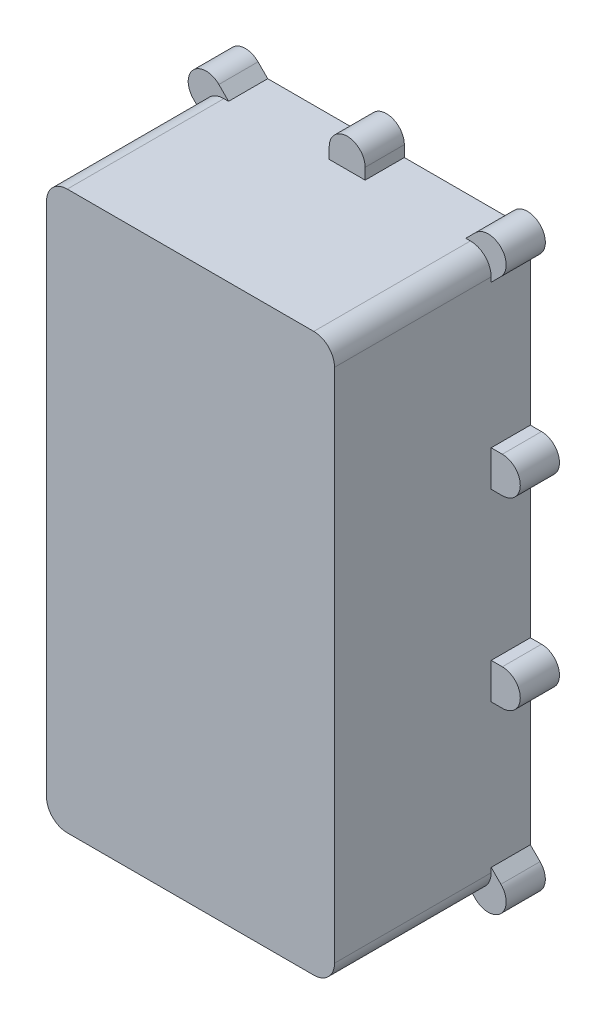
SolidWorks part; units mm, degrees
material "ABS"
ref_plane "X-Y Datum" through (0, 0, 0) normal (0, 0, 1) x (1, 0, 0)
ref_plane "X-Z Datum" through (0, 0, 0) normal (0, 1, 0) x (1, 0, 0)
ref_plane "Y-Z Datum" through (0, 0, 0) normal (1, 0, 0) x (0, 0, -1)
sketch "Sketch1" plane through (0, 0, 0) normal (0, 0, 1) x (1, 0, 0)
  line L0 (1.8162, 48.1563) -> (125.4513, 48.1563) construction
  line L1 (24.3593, 48.1563) -> (24.3593, 120.2923) construction
  line L3 (24.3593, 120.2923) -> (125.4513, 120.2923) construction
  line L8 (125.4513, 48.1563) -> (125.4513, 120.2923) construction
  line L33 (24.3593, 120.2923) -> (1.8162, 120.2923) construction
  line L34 (24.3593, 120.2923) -> (24.3593, 48.1563) construction
  line L35 (63.6337, 48.1563) -> (63.6337, 43.0763) construction
  line L36 (1.8162, 120.2923) -> (1.8162, 48.1563) construction
  line L41 (24.3593, 120.2923) -> (23.7243, 120.2923) construction
  line L42 (24.3593, 120.2923) -> (24.3593, 122.8323) construction
  line L44 (27.5343, 14.7553) -> (27.5343, 43.0763) construction
  line L45 (125.4513, 120.2923) -> (127.9913, 120.2923) construction
  line L46 (27.5343, 14.7553) -> (125.4513, 14.7553) construction
  line L47 (23.7243, 122.8323) -> (127.9913, 122.8323)
  line L48 (23.7243, 122.8323) -> (23.7243, -21.9477)
  line L49 (23.7243, -21.9477) -> (127.9913, -21.9477)
  line L50 (127.9913, 122.8323) -> (127.9913, -21.9477)
  line L51 (125.4513, 14.7553) -> (125.4513, 43.0763) construction
  line L52 (27.5343, 43.0763) -> (125.4513, 43.0763) construction
  line L53 (23.7243, 120.2923) -> (23.7243, 48.1563) construction
  circle A17 centre (30.4553, 114.1963) radius 2.1 construction
  circle A18 centre (119.8633, 115.2123) radius 2.1 construction
  circle A19 centre (119.6813, 54.2533) radius 2.1 construction
  circle A20 centre (29.4393, 53.2363) radius 2.1 construction
  circle A26 centre (31.9793, 18.4383) radius 2.1 construction
  circle A27 centre (31.9793, 39.3933) radius 2.1 construction
  circle A28 centre (120.6193, 28.8183) radius 2.1 construction
sketch "Sketch2" plane through (0, 0, 0) normal (0, 0, 1) x (1, 0, 0)
  line L4 (55.176, 122.8323) -> (127.9913, 122.8323)
  line L6 (55.176, 48.5244) -> (55.176, 50.9244) construction
  line L7 (55.176, -21.05) -> (127.9913, -21.05)
  line L8 (127.9913, 122.8323) -> (127.9913, -21.05)
  line L9 (55.176, 110.2103) -> (127.9913, -21.05) construction
  line L10 (55.176, -8.428) -> (127.9913, 122.8323) construction
  line L11 (55.176, 50.9244) -> (55.176, -21.05)
  line L12 (55.176, 50.9244) -> (55.176, 122.8323)
  circle A7 centre (88.0827, 6.45) radius 27.5
  circle A8 centre (88.0294, 95.3501) radius 27.5
  circle A9 centre (98.216, 50.8911) radius 6.477
  circle A10 centre (77.896, 50.9089) radius 6.477
  circle A11 centre (121.5143, 31.8208) radius 6.477
  circle A12 centre (115.996, 50.8756) radius 2.4
  circle A13 centre (55.176, 50.9244) radius 2.4
  point P14 (88.0827, 50.8911)
sketch "Sketch3" plane through (0, 0, 0) normal (0, 0, 1) x (1, 0, 0)
  line L7 (0, 0) -> (76.2, 0)
  line L10 (0, 0) -> (0, 158.75)
  line L11 (0, 158.75) -> (76.2, 158.75)
  line L12 (76.2, 0) -> (76.2, 158.75)
  dimension "D1" = 158.75
  dimension "D2" = 76.2
extrude "Boss-Extrude1" add sketch "Sketch3" along normal blind 53.975
shell "Shell1" thickness 6 removed face at (38.1, 79.375, 0) outward yes
fillet "Fillet1" radius 5.334 4 edges at (76.2, 158.75, 26.9875) (76.2, 0, 26.9875) (0, 0, 26.9875) (0, 158.75, 26.9875)
fillet "Fillet2" radius 6.35 4 edges at (-6, -6, 29.9875) (-6, 164.75, 29.9875) (82.2, 164.75, 29.9875) (82.2, -6, 29.9875)
sketch "Sketch6" plane through (0, 0, 0) normal (0, 0, -1) x (-1, 0, 0)
  line L8 (-5.334, 163.0327) -> (-70.866, 163.0327)
  line L9 (-80.4827, 153.416) -> (-80.4827, 5.334)
  line L10 (-70.866, -4.2827) -> (-5.334, -4.2827)
  line L11 (4.2827, 5.334) -> (4.2827, 153.416)
  line L12 (-79.2, 153.416) -> (-79.2, 5.334)
  line L13 (-70.866, -3) -> (-5.334, -3)
  line L14 (3, 5.334) -> (3, 153.416)
  line L15 (-5.334, 161.75) -> (-70.866, 161.75)
  line L16 (-79.2, 153.416) -> (-79.2, 5.334) construction
  line L17 (-70.866, -3) -> (-5.334, -3) construction
  line L18 (3, 5.334) -> (3, 153.416) construction
  line L19 (-5.334, 161.75) -> (-70.866, 161.75) construction
  line L20 (-77.9173, 153.416) -> (-77.9173, 5.334)
  line L21 (-70.866, -1.7173) -> (-5.334, -1.7173)
  line L22 (1.7173, 5.334) -> (1.7173, 153.416)
  line L23 (-5.334, 160.4673) -> (-70.866, 160.4673)
  arc A8 (-70.866, 163.0327) -> (-80.4827, 153.416) centre (-70.866, 153.416) ccw
  arc A9 (-80.4827, 5.334) -> (-70.866, -4.2827) centre (-70.866, 5.334) ccw
  arc A10 (-5.334, -4.2827) -> (4.2827, 5.334) centre (-5.334, 5.334) ccw
  arc A11 (4.2827, 153.416) -> (-5.334, 163.0327) centre (-5.334, 153.416) ccw
  arc A12 (-70.866, 161.75) -> (-79.2, 153.416) centre (-70.866, 153.416) ccw
  arc A13 (-79.2, 5.334) -> (-70.866, -3) centre (-70.866, 5.334) ccw
  arc A14 (-5.334, -3) -> (3, 5.334) centre (-5.334, 5.334) ccw
  arc A15 (3, 153.416) -> (-5.334, 161.75) centre (-5.334, 153.416) ccw
  arc A16 (-70.866, 161.75) -> (-79.2, 153.416) centre (-70.866, 153.416) ccw construction
  arc A17 (-79.2, 5.334) -> (-70.866, -3) centre (-70.866, 5.334) ccw construction
  arc A18 (-5.334, -3) -> (3, 5.334) centre (-5.334, 5.334) ccw construction
  arc A19 (3, 153.416) -> (-5.334, 161.75) centre (-5.334, 153.416) ccw construction
  arc A20 (-77.9173, 5.334) -> (-70.866, -1.7173) centre (-70.866, 5.334) ccw
  arc A21 (-5.334, -1.7173) -> (1.7173, 5.334) centre (-5.334, 5.334) ccw
  arc A22 (1.7173, 153.416) -> (-5.334, 160.4673) centre (-5.334, 153.416) ccw
  arc A23 (-70.866, 160.4673) -> (-77.9173, 153.416) centre (-70.866, 153.416) ccw
  dimension "D4" = 7.0513
  dimension "D5" = 2.5654
  dimension "D1" = 3
  dimension "D2" = 1.2827
  dimension "D3" = 1.2827
extrude "Cut-Extrude1" cut sketch "Sketch6" against normal blind 1.2446
fillet "Fillet3" radius 0.254 16 edges at (-4.2827, 79.375, 1.2446) (-1.466, -1.466, 1.2446) (38.1, -4.2827, 1.2446) (77.666, -1.466, 1.2446) (80.4827, 79.375, 1.2446) (77.666, 160.216, 1.2446) (38.1, 163.0327, 1.2446) (-1.466, 160.216, 1.2446) (75.852, 158.402, 1.2446) (77.9173, 79.375, 1.2446) (75.852, 0.348, 1.2446) (38.1, -1.7173, 1.2446) (0.348, 0.348, 1.2446) (-1.7173, 79.375, 1.2446) (0.348, 158.402, 1.2446) (38.1, 160.4673, 1.2446)
fillet "Fillet4" radius 0.127 16 edges at (75.852, 158.402, 0) (38.1, 160.4673, 0) (0.348, 158.402, 0) (-1.7173, 79.375, 0) (0.348, 0.348, 0) (38.1, -1.7173, 0) (75.852, 0.348, 0) (77.666, 160.216, 0) (38.1, 163.0327, 0) (-1.466, 160.216, 0) (-4.2827, 79.375, 0) (-1.466, -1.466, 0) (38.1, -4.2827, 0) (77.666, -1.466, 0) (77.9173, 79.375, 0) (80.4827, 79.375, 0)
sketch "Sketch7" plane through (0, 0, 53.975) normal (0, 0, -1) x (-1, 0, 0)
  line L0 (-76.2, 34.925) -> (0, 34.925)
  line L1 (-76.2, 5.334) -> (-76.2, 153.416) construction
  line L2 (0, 153.416) -> (0, 5.334) construction
  line L3 (-76.2, 37.425) -> (0, 37.425)
  line L4 (-5.334, 0) -> (-70.866, 0) construction
  line L5 (-76.2, 34.925) -> (-76.2, 37.425)
  line L6 (0, 34.925) -> (0, 37.425)
  dimension "D2" = 34.925
  dimension "D1" = 2.5
extrude "Boss-Extrude2" add sketch "Sketch7" along normal up to surface (53.975 mm away) up to face at (38.1, 79.375, 0)
sketch "Sketch8" plane through (0, 0, 0) normal (0, 0, -1) x (-1, 0, 0)
  line L0 (-5.334, 5.334) -> (5.0914, -5.0914)
  line L1 (-1.7782, -6) -> (1.2023, -8.9805)
  line L2 (-0.35, -6) -> (-75.85, -6) construction
  line L3 (-5.334, -4.2827) -> (-5.334, -4.4097)
  line L4 (4.4097, 5.334) -> (4.2827, 5.334)
  line L5 (-5.334, -4.2827) -> (-5.334, -4.4097)
  line L6 (4.4097, 5.334) -> (4.2827, 5.334)
  line L7 (6, 1.7782) -> (8.9805, -1.2023)
  line L8 (6, 158.4) -> (6, 0.35) construction
  line L9 (-38.1, -6) -> (-38.1, 164.75) construction
  line L10 (-75.85, 164.75) -> (-0.35, 164.75) construction
  line L11 (-82.2, 79.375) -> (6, 79.375) construction
  line L12 (-82.2, 0.35) -> (-82.2, 158.4) construction
  circle A0 centre (5.0914, -5.0914) radius 3.025
  circle A1 centre (5.0914, -5.0914) radius 5.5
  arc A3 (-5.334, -4.4097) -> (4.4097, 5.334) centre (-5.334, 5.334) ccw
  arc A4 (-5.334, -4.2827) -> (4.2827, 5.334) centre (-5.334, 5.334) ccw
  arc A5 (-5.334, -4.4097) -> (4.4097, 5.334) centre (-5.334, 5.334) ccw
  arc A6 (-5.334, -4.2827) -> (4.2827, 5.334) centre (-5.334, 5.334) ccw
  point P6 (1.5558, -1.5558)
  arc M11 (4.4097, 5.334) -> (-5.334, -4.4097) centre (-5.334, 5.334) cw
  line M14 (-75.85, -6) -> (-0.35, -6)
  arc M15 (-0.35, -6) -> (6, 0.35) centre (-0.35, 0.35) ccw
  line M16 (6, 0.35) -> (6, 158.4)
  dimension "D1" = 6.05
  dimension "D4" = 11
  dimension "D3" = 5
  dimension "D2" = 0
extrude "Boss-Extrude3" add sketch "Sketch8" against normal blind 12 contours A1 A0 M15 | A1 L1 M15 M14 | A1 L7 M16 M15 | A0 M15 | L0 A0 M15 | A0 L0 M15 | A1 A0 L0 M11 M15 | A1 L0 A0 M15 M11 region at (-3.9532, -1.0787, 0) region at (-1.0787, -3.9532, 0) region at (-4.2457, -2.9327, 0) region at (-2.9327, -4.2457, 0) region at (-6.789, 0.5448, 0) region at (-7.5393, -0.3393, 0) region at (0.5448, -6.789, 0) region at (-5.4552, -5.4552, 0)
sketch "Sketch9" plane through (0, 0, 0) normal (0, 0, -1) x (-1, 0, 0)
  circle A0 centre (5.0914, -5.0914) radius 3.025 construction
  circle A1 centre (5.0914, -5.0914) radius 3.025
  dimension "D1" = 6.05
extrude "Cut-Extrude2" cut sketch "Sketch9" against normal blind 9
ref_plane "Plane1" through (38.1, 0, 0) normal (-1, 0, 0) x (0, 0, 1)
ref_plane "Plane2" through (0, 79.375, 0) normal (0, -1, 0) x (-1, 0, 0)
mirror "Mirror1" about plane through (38.1, 0, 0) normal (-1, 0, 0) of "Cut-Extrude2", "Boss-Extrude3"
mirror "Mirror2" about plane through (0, 79.375, 0) normal (0, -1, 0) of "Cut-Extrude2", "Boss-Extrude3", "Mirror1"
sketch "Sketch10" plane through (0, 0, 0) normal (0, 0, -1) x (-1, 0, 0)
  line L0 (6, 79.375) -> (39.3327, 79.375) construction
  line L2 (6, 156.9718) -> (6, 1.7782) construction
  line L3 (6, 79.375) -> (6, 157.4914)
  line L4 (6, 107.569) -> (9.4097, 107.569) construction
  line L5 (4.4097, 153.416) -> (4.4097, 5.334) construction
  line L7 (9.4097, 113.069) -> (6, 113.069)
  line L9 (9.4097, 102.069) -> (6, 102.069)
  line L10 (9.4097, 45.681) -> (6, 45.681)
  line L11 (9.4097, 56.681) -> (6, 56.681)
  circle A4 centre (9.4097, 107.569) radius 3.025
  circle A5 centre (9.4097, 107.569) radius 5.5
  circle A6 centre (9.4097, 51.181) radius 3.025
  circle A7 centre (9.4097, 51.181) radius 5.5
  point P0 (5.0914, 163.8414)
  point P1 (5.0914, -5.0914)
  point P3 (-81.2914, -5.0914)
  line M14 (6, 1.7782) -> (6, 156.9718)
  line M21 (4.4097, 153.416) -> (4.4097, 5.334)
  dimension "D3" = 84.4664
  dimension "D4" = 6.05
  dimension "D5" = 11
  dimension "D1" = 168.9327
  dimension "D2" = 86.3827
  dimension "D6" = 5
  dimension "D7" = 28.194
  dimension "D8" = 56.2724
  dimension "D9" = 56.388
  dimension "D10" = 56.2724
extrude "Boss-Extrude4" add sketch "Sketch10" against normal blind 12 contours A7 A6 M14 | A7 L11 M14 | A7 M14 M21 | L10 A7 M14 | A6 | A5 L7 L3 | A5 L3 L9 | A5 A4 M14 | A5 M14 M21 | A4 region at (-6.833, 102.4167, 0) region at (-6.833, 56.3333, 0) region at (-5.2799, 107.569, 0) region at (-6.1416, 107.569, 0) region at (-13.1987, 54.97, 0) region at (-5.2799, 51.181, 0) region at (-6.833, 112.7213, 0) region at (-6.833, 46.0287, 0) region at (-9.4097, 107.569, 0) region at (-9.4097, 51.181, 0)
sketch "Sketch11" plane through (0, 0, 0) normal (0, 0, -1) x (-1, 0, 0)
  circle A0 centre (9.4097, 51.181) radius 3.025 construction
  circle A1 centre (9.4097, 107.569) radius 3.025 construction
  circle A2 centre (9.4097, 51.181) radius 3.025
  circle A3 centre (9.4097, 107.569) radius 3.025
  dimension "D1" = 6.05
extrude "Cut-Extrude3" cut sketch "Sketch11" against normal blind 9
mirror "Mirror3" about plane through (38.1, 0, 0) normal (-1, 0, 0) of "Cut-Extrude3", "Boss-Extrude4"
sketch "Sketch12" plane through (0, 0, 0) normal (0, 0, -1) x (-1, 0, 0)
  line L0 (-74.4218, -6) -> (-1.7782, -6)
  line L1 (-38.1, -6) -> (-38.1, -9.4097) construction
  line L2 (-5.334, -4.4097) -> (-70.866, -4.4097) construction
  line L3 (-43.6, -9.4097) -> (-43.6, -6)
  line L4 (-32.6, -9.4097) -> (-32.6, -6)
  circle A0 centre (-38.1, -9.4097) radius 3.025
  circle A1 centre (-38.1, -9.4097) radius 5.5
  point P15 (-81.2914, -5.0914)
  point P16 (5.0914, -5.0914)
  line M16 (-74.4218, -6) -> (-1.7782, -6)
  line M42 (-5.334, -4.4097) -> (-70.866, -4.4097)
  dimension "D2" = 6.05
  dimension "D4" = 11
  dimension "D1" = 43.1914
  dimension "D3" = 5
  dimension "D5" = 86.3827
extrude "Boss-Extrude5" add sketch "Sketch12" against normal blind 12 contours A1 L0 A0 M16 | A1 L0 L3 | A1 L4 L0 | A0 | L0 A1 M16 M42 region at (43.2523, -6.833, 0) region at (38.1, -5.2799, 0) region at (38.1, -6.1416, 0) region at (32.9477, -6.833, 0) region at (38.1, -9.4097, 0)
sketch "Sketch13" plane through (0, 0, 0) normal (0, 0, -1) x (-1, 0, 0)
  circle A0 centre (-38.1, -9.4097) radius 3.025 construction
  circle A1 centre (-38.1, -9.4097) radius 3.025
extrude "Cut-Extrude4" cut sketch "Sketch13" against normal blind 9
mirror "Mirror4" about plane through (0, 79.375, 0) normal (0, -1, 0) of "Cut-Extrude4", "Boss-Extrude5"
sketch "Sketch17" plane through (-6, 0, 0) normal (-1, 0, 0) x (0, 0, 1)
  line L0 (59.975, 158.4) -> (59.975, 0.35) construction
  line L1 (0, 37.425) -> (53.975, 37.425) construction
  line L2 (53.975, 34.925) -> (53.975, 5.334) construction
  circle A0 centre (38.385, 119.975) radius 9.525
  circle A1 centre (38.385, 119.975) radius 14.2875
  circle A2 centre (38.385, 20.1295) radius 6.35
  circle A3 centre (38.385, 20.1295) radius 10.795
  point P10 (53.975, 20.1295)
  dimension "D1" = 19.05
  dimension "D4" = 28.575
  dimension "D5" = 12.7
  dimension "D6" = 21.59
  dimension "D2" = 21.59
  dimension "D3" = 82.55
extrude "Cut-Extrude6" cut sketch "Sketch17" against normal blind 6 contours A0 | A2 region at (-6, 119.975, 38.385) region at (-6, 20.1295, 38.385)
sketch "Sketch18" plane through (0, 0, 0) normal (1, 0, 0) x (0, 0, -1)
  circle A0 centre (-38.385, 119.975) radius 14.2875 construction
  circle A1 centre (-38.385, 119.975) radius 14.2875
  circle A2 centre (-38.385, 20.1295) radius 10.795 construction
  circle A3 centre (-38.385, 20.1295) radius 10.795
extrude "Cut-Extrude7" cut sketch "Sketch18" against normal blind 3
